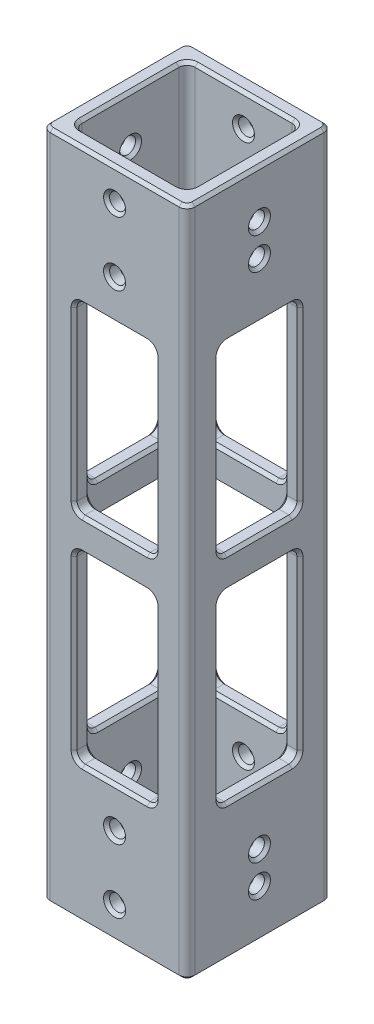
SolidWorks part; units mm, degrees
note: '?' marks a value the reader was unsure of.
ref_plane "Front Plane" through (0, 0, 0) normal (0, 0, 1) x (1, 0, 0)
ref_plane "Top Plane" through (0, 0, 0) normal (0, 1, 0) x (1, 0, 0)
ref_plane "Right Plane" through (0, 0, 0) normal (1, 0, 0) x (0, 0, -1)
sketch "Sketch1" plane through (0, 0, 0) normal (0, 1, 0) x (1, 0, 0)
  line L1 (-14.3891, -14.3891) -> (14.3891, -14.3891)
  line L2 (-14.3891, -14.3891) -> (-14.3891, 14.3891)
  line L3 (-14.3891, 14.3891) -> (14.3891, 14.3891)
  line L4 (14.3891, -14.3891) -> (14.3891, 14.3891)
  line L5 (-14.3891, -14.3891) -> (14.3891, 14.3891) construction
  line L6 (-14.3891, 14.3891) -> (14.3891, -14.3891) construction
  line L7 (-11.2204, -11.2204) -> (11.2204, -11.2204)
  line L8 (-11.2204, -11.2204) -> (-11.2204, 11.2205)
  line L9 (-11.2204, 11.2205) -> (11.2204, 11.2205)
  line L10 (11.2204, -11.2204) -> (11.2204, 11.2205)
  line L11 (-11.2204, -11.2204) -> (11.2204, 11.2205) construction
  line L12 (-11.2204, 11.2205) -> (11.2204, -11.2204) construction
  point P0 (0, 0)
  point P6 (0, 0)
  dimension "D1" = 28.7782
  dimension "D2" = 28.7782
  dimension "D3" = 22.4409
extrude "Boss-Extrude1" add sketch "Sketch1" along normal mid plane 133.35 contours L3 L4 L1 L2
hole_wizard "1/8 (0.125) Diameter Hole1" positions "Sketch8" profile "Sketch9" hole size "1/8" standard "ANSI Inch" end condition through all
sketch "Sketch8" plane through (-14.3891, 0, 0) normal (-1, 0, 0) x (0, 0, 1)
  line L2 (0, 57.15) -> (0, 66.675) construction
  line L3 (-14.3891, 66.675) -> (14.3891, 66.675) construction
  point P0 (0, 57.15)
  point P2 (0, 50.8)
  dimension "D1" = 6.35
  dimension "D2" = 9.525
sketch "Sketch9" plane through (-14.3891, 57.15, 0) normal (0, 1, 0) x (0, 0, 1)
  line L0 (0, 0) -> (0, 28.7782)
  line L1 (0, 28.7782) -> (1.5875, 28.7782)
  line L2 (1.5875, 28.7782) -> (1.5875, 0)
  line L5 (1.5875, 0) -> (0, 0)
  line L11 (0, -6.35) -> (0, 107.95) construction
  dimension "Thru Hole Dia." = 3.175
  dimension "Thru Hole Depth" = 28.7782
hole_wizard "1/8 (0.125) Diameter Hole2" positions "Sketch10" profile "Sketch11" hole size "1/8" standard "ANSI Inch" end condition through all
sketch "Sketch10" plane through (14.3891, 0, 0) normal (1, 0, 0) x (0, 0, -1)
  line L0 (0, -66.675) -> (0, -57.15) construction
  line L1 (-14.3891, -66.675) -> (14.3891, -66.675) construction
  point P0 (0, -50.8)
  point P2 (0, -57.15)
  dimension "D1" = 6.35
  dimension "D2" = 9.525
sketch "Sketch11" plane through (14.3891, -50.8, 0) normal (0, 1, 0) x (0, 0, -1)
  line L0 (0, 0) -> (0, 28.7782)
  line L1 (0, 28.7782) -> (1.5875, 28.7782)
  line L2 (1.5875, 28.7782) -> (1.5875, 0)
  line L5 (1.5875, 0) -> (0, 0)
  line L11 (0, -6.35) -> (0, 107.95) construction
  dimension "Thru Hole Dia." = 3.175
  dimension "Thru Hole Depth" = 28.7782
hole_wizard "1/8 (0.125) Diameter Hole3" positions "Sketch16" profile "Sketch17" hole size "1/8" standard "ANSI Inch" end condition through all
sketch "Sketch16" plane through (0, 0, 14.3891) normal (0, 0, 1) x (1, 0, 0)
  line L0 (0, -60.325) -> (0, -66.675) construction
  line L1 (-14.3891, -66.675) -> (14.3891, -66.675) construction
  line L3 (0, -47.625) -> (0, -60.325) construction
  line L5 (0, 60.325) -> (0, 66.675) construction
  line L6 (-14.3891, 66.675) -> (14.3891, 66.675) construction
  line L8 (0, 47.625) -> (0, 60.325) construction
  point P0 (0, 60.325)
  point P2 (0, 47.625)
  point P4 (0, -47.625)
  point P6 (0, -60.325)
  dimension "D1" = 6.35
  dimension "D2" = 12.7
sketch "Sketch17" plane through (0, 60.325, 14.3891) normal (1, 0, 0) x (0, -1, 0)
  line L0 (0, 0) -> (0, 28.7782)
  line L1 (0, 28.7782) -> (1.5875, 28.7782)
  line L2 (1.5875, 28.7782) -> (1.5875, 0)
  line L5 (1.5875, 0) -> (0, 0)
  line L11 (0, -6.35) -> (0, 107.95) construction
  dimension "Thru Hole Dia." = 3.175
  dimension "Thru Hole Depth" = 28.7782
sketch "Sketch15" plane through (0, 0, 0) normal (0, 0, 1) x (1, 0, 0)
  line L0 (-8.0391, 39.6875) -> (8.0391, 39.6875) construction
  line L3 (8.0391, 39.6875) -> (8.0391, -39.6875) construction
  line L8 (8.0391, -39.6875) -> (-8.0391, -39.6875) construction
  line L11 (-8.0391, -39.6875) -> (-8.0391, 39.6875) construction
  line L12 (0, -46.0375) -> (0, -39.6875) construction
  line L13 (0, 46.0375) -> (0, 39.6875) construction
  line L23 (-8.0391, 3.175) -> (8.0391, 3.175) construction
  line L24 (-8.0391, -3.175) -> (8.0391, -3.175) construction
  line L28 (0, -3.175) -> (0, 3.175) construction
  line L30 (-8.0391, 39.6875) -> (8.0391, 39.6875)
  line L32 (-8.0391, 3.175) -> (-8.0391, 39.6875)
  line L39 (-14.3891, 66.675) -> (-14.3891, -66.675) construction
  line L68 (8.0391, 39.6875) -> (8.0391, 3.175)
  line L74 (-8.0391, 3.175) -> (8.0391, 3.175)
  line L88 (-8.0391, -3.175) -> (8.0391, -3.175)
  line L91 (-8.0391, -39.6875) -> (-8.0391, -3.175)
  line L92 (8.0391, -3.175) -> (8.0391, -39.6875)
  line L101 (-8.0391, -39.6875) -> (8.0391, -39.6875)
  circle A7 centre (0, -47.625) radius 1.5875 construction
  circle A8 centre (0, 47.625) radius 1.5875 construction
  dimension "D1" = 6.35
  dimension "D2" = 6.35
  dimension "D4" = 6.35
extrude "Cut-Extrude1" cut sketch "Sketch15" against normal up to next
ref_axis "Axis2" through (0, -73.3425, 0) along (0, 1, 0)?
pattern_circular "CirPattern2" count 4 over 360 about axis through (0, 0, 0) along (0, 1, 0) of "Cut-Extrude1"
fillet "Fillet1_1/32_Outer&Inner)" radius 1.5875 8 edges at (14.3891, 0, -14.3891) (14.3891, 0, 14.3891) (-14.3891, 0, -14.3891) (-14.3891, 0, 14.3891) (11.2204, 0, -11.2205) (11.2204, 0, 11.2204) (-11.2204, 0, 11.2204) (-11.2204, 0, -11.2205)
fillet "Fillet1_1/32_(holes)" radius 1.5875 32 edges at (-12.8048, -39.6875, 8.0391) (-12.8048, -39.6875, -8.0391) (-12.8048, -3.175, -8.0391) (-12.8048, -3.175, 8.0391) (-12.8048, 3.175, -8.0391) (-12.8048, 3.175, 8.0391) (-12.8048, 39.6875, 8.0391) (-12.8048, 39.6875, -8.0391) (-8.0391, 39.6875, -12.8048) (8.0391, 39.6875, -12.8048) (8.0391, -3.175, -12.8048) (-8.0391, -3.175, -12.8048) (8.0391, 3.175, -12.8048) (-8.0391, 3.175, -12.8048) (-8.0391, -39.6875, -12.8048) (8.0391, -39.6875, -12.8048) (12.8048, -39.6875, 8.0391) (12.8048, -39.6875, -8.0391) (12.8048, 3.175, -8.0391) (12.8048, 3.175, 8.0391) (12.8048, -3.175, 8.0391) (12.8048, -3.175, -8.0391) (12.8048, 39.6875, -8.0391) (12.8048, 39.6875, 8.0391) (-8.0391, 39.6875, 12.8048) (8.0391, 39.6875, 12.8048) (8.0391, -3.175, 12.8048) (-8.0391, -3.175, 12.8048) (8.0391, 3.175, 12.8048) (-8.0391, 3.175, 12.8048) (8.0391, -39.6875, 12.8048) (-8.0391, -39.6875, 12.8048)
chamfer "Chamfer2_3/128" distance 0.5953 angle 45 192 edges at (0, -66.675, -14.3891) (0, 66.675, -14.3891) (14.3891, -66.675, 0) (0, -66.675, 14.3891) (-14.3891, -66.675, 0) (0, -66.675, 11.2204) (11.2204, -66.675, 0) (0, -66.675, -11.2205) (-11.2204, -66.675, 0) (-13.9241, -66.675, 13.9241) (-13.9241, -66.675, -13.9241) (13.9241, -66.675, 13.9241) (13.9241, -66.675, -13.9241) (14.3891, 66.675, 0) (-14.3891, 66.675, 0) (0, 66.675, 14.3891) (11.2204, 66.675, 0) (0, 66.675, 11.2204) (-11.2204, 66.675, 0) (0, 66.675, -11.2205) (-13.9241, 66.675, 13.9241) (-13.9241, 66.675, -13.9241) (13.9241, 66.675, 13.9241) (13.9241, 66.675, -13.9241) (10.7555, -66.675, -10.7555) (10.7555, 66.675, -10.7555) (10.7555, -66.675, 10.7555) (10.7555, 66.675, 10.7555) (-10.7555, -66.675, 10.7555) (-10.7555, 66.675, 10.7555) (-10.7555, -66.675, -10.7555) (-10.7555, 66.675, -10.7555) (-14.3891, -39.6875, 0) (-11.2204, -39.6875, 0) (-14.3891, -21.4313, 8.0391) (-11.2204, -21.4313, 8.0391) (-14.3891, -21.4312, -8.0391) (-11.2204, -21.4312, -8.0391) (-14.3891, -3.175, 0) (-11.2204, -3.175, 0) (-14.3891, 21.4313, -8.0391) (-11.2204, 21.4313, -8.0391) (-14.3891, 3.175, 0) (-11.2204, 3.175, 0) (-14.3891, 21.4312, 8.0391) (-11.2204, 21.4312, 8.0391) (-14.3891, 39.6875, 0) (-11.2204, 39.6875, 0) (-8.0391, 21.4312, -14.3891) (-8.0391, 21.4312, -11.2205) (0, 39.6875, -14.3891) (0, 39.6875, -11.2205) (8.0391, 21.4312, -14.3891) (8.0391, 21.4312, -11.2205) (0, -3.175, -14.3891) (0, -3.175, -11.2205) (8.0391, -21.4312, -14.3891) (8.0391, -21.4312, -11.2205) (-8.0391, -21.4312, -14.3891) (-8.0391, -21.4312, -11.2205) (0, 3.175, -14.3891) (0, 3.175, -11.2205) (0, -39.6875, -14.3891) (0, -39.6875, -11.2205) (14.3891, -21.4312, 8.0391) (11.2204, -21.4312, 8.0391) (14.3891, -39.6875, 0) (11.2204, -39.6875, 0) (14.3891, -21.4312, -8.0391) (11.2204, -21.4312, -8.0391) (14.3891, 3.175, 0) (11.2204, 3.175, 0) (14.3891, 21.4312, -8.0391) (11.2204, 21.4312, -8.0391) (14.3891, 21.4312, 8.0391) (11.2204, 21.4312, 8.0391) (14.3891, -3.175, 0) (11.2204, -3.175, 0) (14.3891, 39.6875, 0) (11.2204, 39.6875, 0) (0, 39.6875, 14.3891) (0, 39.6875, 11.2204) (-8.0391, 21.4313, 14.3891) (-8.0391, 21.4313, 11.2204) (8.0391, 21.4312, 14.3891) (8.0391, 21.4312, 11.2204) (8.0391, -21.4313, 14.3891) (8.0391, -21.4313, 11.2204) (0, -3.175, 14.3891) (0, -3.175, 11.2204) (-11.2204, 50.8, -1.5875) (-8.0391, -21.4312, 14.3891) (11.2204, 50.8, 1.5875) (-8.0391, -21.4312, 11.2204) (14.3891, 50.8, 1.5875) (0, 3.175, 14.3891) (-14.3891, 50.8, 1.5875) (0, 3.175, 11.2204) (0, -39.6875, 14.3891) (0, -39.6875, 11.2204) (-11.2204, -39.2225, 7.5741) (-14.3891, -39.2225, 7.5741) (-11.2204, -39.2225, -7.5741) (-14.3891, -39.2225, -7.5741) (-11.2204, -3.64, -7.5741) (-14.3891, -3.64, -7.5741) (-11.2204, -3.64, 7.5741) (-14.3891, -3.64, 7.5741) (-11.2204, 3.64, -7.5741) (-14.3891, 3.64, -7.5741) (-11.2204, 3.64, 7.5741) (-14.3891, 3.64, 7.5741) (-11.2204, 39.2225, 7.5741) (-14.3891, 39.2225, 7.5741) (-11.2204, 39.2225, -7.5741) (-14.3891, 39.2225, -7.5741) (-7.5741, 39.2225, -11.2205) (-7.5741, 39.2225, -14.3891) (7.5741, 39.2225, -11.2205) (7.5741, 39.2225, -14.3891) (7.5741, -3.64, -11.2205) (7.5741, -3.64, -14.3891) (-7.5741, -3.64, -11.2205) (-7.5741, -3.64, -14.3891) (7.5741, 3.64, -11.2205) (7.5741, 3.64, -14.3891) (-7.5741, 3.64, -11.2205) (-7.5741, 3.64, -14.3891) (-7.5741, -39.2225, -11.2205) (-7.5741, -39.2225, -14.3891) (7.5741, -39.2225, -11.2205) (7.5741, -39.2225, -14.3891) (11.2204, -39.2225, 7.5741) (14.3891, -39.2225, 7.5741) (11.2204, -39.2225, -7.5741) (14.3891, -39.2225, -7.5741) (11.2204, 3.64, -7.5741) (14.3891, 3.64, -7.5741) (11.2204, 3.64, 7.5741) (14.3891, 3.64, 7.5741) (11.2204, -3.64, 7.5741) (14.3891, -3.64, 7.5741) (11.2204, -3.64, -7.5741) (14.3891, -3.64, -7.5741) (11.2204, 39.2225, -7.5741) (14.3891, 39.2225, -7.5741) (11.2204, 39.2225, 7.5741) (14.3891, 39.2225, 7.5741) (-7.5741, 39.2225, 11.2204) (-7.5741, 39.2225, 14.3891) (7.5741, 39.2225, 11.2204) (7.5741, 39.2225, 14.3891) (7.5741, -3.64, 11.2204) (7.5741, -3.64, 14.3891) (-7.5741, -3.64, 11.2204) (-7.5741, -3.64, 14.3891) (7.5741, 3.64, 11.2204) (7.5741, 3.64, 14.3891) (-7.5741, 3.64, 11.2204) (-7.5741, 3.64, 14.3891) (7.5741, -39.2225, 11.2204) (7.5741, -39.2225, 14.3891) (-7.5741, -39.2225, 11.2204) (-7.5741, -39.2225, 14.3891) (11.2204, 57.15, 1.5875) (-11.2204, 57.15, -1.5875) (-14.3891, 57.15, 1.5875) (14.3891, 57.15, 1.5875) (-11.2204, -57.15, -1.5875) (11.2204, -57.15, 1.5875) (14.3891, -57.15, -1.5875) (-14.3891, -57.15, -1.5875) (-11.2204, -50.8, -1.5875) (11.2204, -50.8, 1.5875) (14.3891, -50.8, -1.5875) (-14.3891, -50.8, -1.5875) (1.5875, -60.325, -11.2204) (-1.5875, -60.325, 11.2204) (1.5875, -60.325, 14.3891) (1.5875, -60.325, -14.3891) (1.5875, -47.625, -11.2204) (-1.5875, -47.625, 11.2204) (1.5875, -47.625, 14.3891) (1.5875, -47.625, -14.3891) (-1.5875, 47.625, 11.2204) (1.5875, 47.625, -11.2204) (1.5875, 47.625, -14.3891) (1.5875, 47.625, 14.3891) (-1.5875, 60.325, 11.2204) (1.5875, 60.325, -11.2204) (1.5875, 60.325, -14.3891) (1.5875, 60.325, 14.3891)
equation "\"D2@Sketch1\"=\"D1@Sketch1\""
